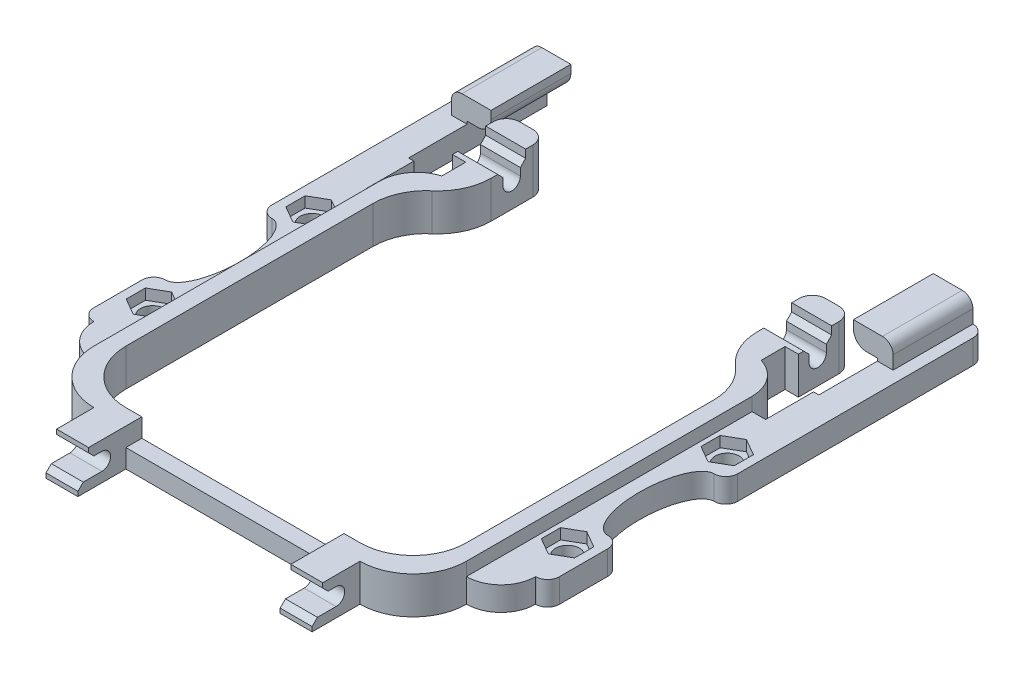
SolidWorks part; units mm, degrees
ref_plane "Front Plane" through (0, 0, 0) normal (0, 0, 1) x (1, 0, 0)
ref_plane "Top Plane" through (0, 0, 0) normal (0, 1, 0) x (1, 0, 0)
ref_plane "Right Plane" through (0, 0, 0) normal (1, 0, 0) x (0, 0, -1)
sketch "Sketch1" plane through (0, 0, 0) normal (0, 1, 0) x (1, 0, 0)
  line L0 (-19, -36) -> (-19, -19.5429) construction
  line L1 (-19, -36) -> (19, -36)
  line L3 (0, 36) -> (25, 36) construction
  line L4 (35, -36) -> (35, 36)
  line L5 (-35, -36) -> (35, 36) construction
  line L6 (-35, 36) -> (35, -36) construction
  line L7 (19, -36) -> (19, -19.5429) construction
  line L8 (0, 36) -> (0, -36) construction
  line L9 (19, -45) -> (25, -45)
  line L11 (-19, -36) -> (-19, -45)
  line L12 (-19, -45) -> (-25, -45)
  line L13 (-25, -36) -> (-25, -45)
  line L14 (25, -36) -> (25, -45)
  line L15 (19, -36) -> (19, -45)
  line L16 (-32.5, 40) -> (32.5, 40) construction
  line L17 (-41.1406, 49) -> (44.3921, 49) construction
  line L18 (-35, -36) -> (-25, -36)
  line L19 (-25, 36) -> (-25, 25.7143) construction
  line L20 (25, 36) -> (25, 25.7143) construction
  line L21 (25, -36) -> (35, -36) construction
  line L23 (-25, 36) -> (-25, 49)
  line L24 (-25, 49) -> (-32.5, 49)
  line L25 (-32.5, 36) -> (-32.5, 49)
  line L26 (-32, 33) -> (-32, -33)
  line L27 (25, 36) -> (25, 49)
  line L28 (25, 49) -> (32.5, 49)
  line L29 (32.5, 36) -> (32.5, 49)
  line L37 (-35, 36) -> (-32.5, 36)
  line L39 (35, 36) -> (32.5, 36)
  line L40 (-35, 36) -> (-35, -36)
  line L42 (25, -36) -> (35, -36)
  line L50 (32, -33) -> (32, 33)
  line L60 (-28, 33) -> (-28, 46) construction
  line L61 (-29.5, 33) -> (-29.5, 46) construction
  line L62 (-28, 46) -> (-29.5, 46) construction
  line L63 (29.5, 33) -> (29.5, 46) construction
  line L64 (28, 46) -> (29.5, 46) construction
  line L65 (28, 33) -> (28, 46) construction
  line L66 (22, -33) -> (22, -42) construction
  line L67 (22, -33) -> (22, -42) construction
  line L68 (22, -42) -> (22, -42) construction
  line L69 (-22, -33) -> (-22, -42) construction
  line L70 (-22, -33) -> (-22, -42) construction
  line L71 (-22, -42) -> (-22, -42) construction
  line L72 (-32, -33) -> (-22, -33) construction
  line L73 (22, -33) -> (32, -33) construction
  line L74 (-22, -33) -> (22, -33) construction
  line L75 (-32, 33) -> (-29.5, 33) construction
  line L76 (-28, 33) -> (28, 33) construction
  line L77 (32, 33) -> (29.5, 33) construction
  line L78 (-32, 33) -> (-25, 33)
  line L79 (-32, -33) -> (32, -33)
  line L80 (-25, 36) -> (-25, 33)
  line L81 (25, 36) -> (25, 33)
  line L82 (-25, 36) -> (0, 36) construction
  line L83 (-25, 36) -> (25, 36) construction
  line L85 (25, 33) -> (32, 33)
  dimension "D3" = 50
  dimension "D7" = 3
  dimension "D1" = 70
  dimension "D2" = 72
  dimension "D4" = 38
  dimension "D5" = 6
  dimension "D6" = 9
  dimension "D8" = 76
  dimension "D9" = 85
  dimension "D10" = 66
  dimension "D13" = 7.5
  dimension "D14" = 13
extrude "Boss-Extrude1" add sketch "Sketch1" along normal blind 7
sketch "Sketch2" plane through (25, 0, 0) normal (1, 0, 0) x (0, 0, -1)
  line L0 (-36, 0) -> (-45, 0) construction
  line L1 (-45, 7) -> (-36, 7)
  line L2 (-45, 7) -> (-45, 0)
  line L3 (-45, 0) -> (-36, 0)
  line L4 (-36, 7) -> (-36, 0)
  line L5 (-36, 7) -> (-36, 0) construction
  line L6 (-45, 7) -> (-36, 0) construction
  line L7 (-36, 7) -> (-45, 0) construction
  line L8 (-40.5, 5.125) -> (-45, 5.125)
  line L9 (-40.5, 1.875) -> (-45, 1.875)
  line L10 (-43, 5.125) -> (-43, 7)
  line L11 (-43, 7) -> (-45, 7)
  line L12 (-45, 5.125) -> (-45, 7)
  line L13 (-45, 5.125) -> (-43, 5.125)
  arc A0 (-40.5, 1.875) -> (-40.5, 5.125) centre (-40.5, 3.5) ccw
  line M7 (-45, 7) -> (-45, 0)
  dimension "D1" = 3.25
  dimension "D2" = 2
extrude "Cut-Extrude2" cut sketch "Sketch2" against normal up to surface (50 mm away) contours A0 | L8 L10 L1 M7 region at (25, 6.0625, 44) region at (25, 3.5, 42.1005) up to face at (-25, 3.5, 40.5)
sketch "Sketch3" plane through (32.5, 0, 0) normal (1, 0, 0) x (0, 0, -1)
  line L1 (49, 0) -> (36, 0)
  line L2 (49, 0) -> (49, 7)
  line L3 (49, 7) -> (36, 7)
  line L4 (36, 0) -> (36, 7)
  line L6 (44.125, 4.625) -> (44.125, 7)
  line L7 (40.875, 4.625) -> (40.875, 7)
  arc A0 (40.875, 4.625) -> (44.125, 4.625) centre (42.5, 4.625) ccw
  point P7 (42.5, 3)
  dimension "D1" = 3.25
  dimension "D2" = 3
sketch "Sketch4" plane through (0, 0, 0) normal (0, -1, 0) x (1, 0, 0)
  line L0 (0, -67.5) -> (0, 45) construction
  line L1 (41.5, 45) -> (-41.5, 45)
  line L3 (41.5, -67.5) -> (-41.5, -67.5)
  line L5 (19, 45) -> (25, 45) construction
  line L7 (-41.5, -5) -> (41.5, -5) construction
  line L13 (-41.5, 45) -> (-41.5, -67.5)
  line L15 (41.5, 45) -> (41.5, -67.5)
  point P0 (0, 0)
  dimension "D1" = 83
  dimension "D2" = 112.5
  dimension "D7" = 5
ref_plane "Plane1" through (0, 0, -33) normal (0, 0, 1) x (1, 0, 0)
extrude "Cut-Extrude5" cut sketch "Sketch3" against normal up to surface (65 mm away) from surface contours L7 A0 L6 L3 region at (32.5, 5.1564, -42.5) up to face at (-32.5, 3.5, -42.5) starting at face at (32.5, 3.5, -42.5)
sketch "Sketch9" plane through (0, 7, 0) normal (0, 1, 0) x (1, 0, 0)
  line L1 (35, 38.875) -> (30, 38.875)
  line L2 (35, 38.875) -> (35, 34.375)
  line L3 (35, 34.375) -> (30, 34.375)
  line L4 (30, 38.875) -> (30, 34.375)
  line L5 (25, 40.875) -> (32.5, 40.875) construction
  line L6 (35, -36) -> (35, 36) construction
  dimension "D1" = 2
  dimension "D2" = 4.5
  dimension "D3" = 5
ref_plane "Plane2" through (0, 0, 0) normal (-1, 0, 0) x (0, 0, 1)
extrude "Cut-Extrude8" cut sketch "Sketch9" against normal up to vertex (7 mm away) up to point (32.5, 0, -36)
mirror "Mirror1" about plane through (0, 0, 0) normal (-1, 0, 0) of "Cut-Extrude8"
fillet "Fillet1" radius 7 2 edges at (35, 3.5, -34.375) (-35, 3.5, -34.375)
fillet "Fillet3" radius 10 2 edges at (32, 3.5, -33) (-32, 3.5, -33)
fillet "Fillet5" radius 10 2 edges at (35, 3.5, 36) (-35, 3.5, 36)
fillet "Fillet6" radius 10 2 edges at (32, 3.5, 33) (-32, 3.5, 33)
fillet "Fillet7" radius 10 2 edges at (25, 3.5, -33) (-25, 3.5, -33)
fillet "Fillet8" radius 2.5 4 edges at (32.5, 3.5, -49) (25, 3.5, -49) (-25, 3.5, -49) (-32.5, 3.5, -49)
chamfer "Chamfer2" distance 1 angle 45 4 edges at (28.75, 7, -40.875) (28.75, 7, -44.125) (-28.75, 7, -40.875) (-28.75, 7, -44.125)
sketch "Sketch20" plane through (0, 0, 36) normal (0, 0, 1) x (1, 0, 0)
  line L0 (19, 7) -> (19, 0) construction
  line L1 (-19, 7) -> (19, 7)
  line L2 (-19, 7) -> (-19, 3.5)
  line L3 (-19, 3.5) -> (19, 3.5)
  line L4 (19, 7) -> (19, 3.5)
  dimension "D1" = 3.5
extrude "Cut-Extrude7" cut sketch "Sketch20" against normal up to next
sketch "Sketch22" plane through (-35, 0, 0) normal (-1, 0, 0) x (0, 0, 1)
  line L1 (-27.6668, 4.5) -> (26, 4.5)
  line L2 (-27.6668, 4.5) -> (-27.6668, 0)
  line L3 (-27.6668, 0) -> (26, 0)
  line L4 (26, 4.5) -> (26, 0)
  line L9 (-27.6668, 0) -> (26, 0) construction
  line L11 (-27.6668, 7) -> (-27.6668, 0) construction
  line L12 (26, 0) -> (26, 7) construction
  dimension "D1" = 4.5
extrude "Boss-Extrude9" add sketch "Sketch22" along normal up to vertex (6.5 mm away) up to point (-41.5, 0, 45)
sketch "Sketch24" plane through (0, 0, -27.6668) normal (0, 0, -1) x (-1, 0, 0)
  line L1 (41.5, 0) -> (37.55, 0)
  line L2 (41.5, 0) -> (41.5, 4.5)
  line L3 (41.5, 4.5) -> (37.55, 4.5)
  line L4 (37.55, 0) -> (37.55, 4.5)
  line L7 (41.5, 4.5) -> (35, 4.5) construction
  dimension "D1" = 3.95
extrude "Boss-Extrude11" add sketch "Sketch24" along normal blind 35
sketch "Sketch25" plane through (0, 4.5, 0) normal (0, 1, 0) x (1, 0, 0)
  line L0 (-41.5, -45) -> (-41.5, 67.5) construction
  line L1 (-37.55, 62.6668) -> (-41.5, 62.6668)
  line L2 (-37.55, 62.6668) -> (-37.55, 47.6668)
  line L3 (-37.55, 47.6668) -> (-41.5, 47.6668)
  line L4 (-41.5, 62.6668) -> (-41.5, 47.6668)
  dimension "D1" = 15
extrude "Boss-Extrude12" add sketch "Sketch25" along normal blind 4.5
sketch "Sketch28" plane through (-37.55, 0, 0) normal (1, 0, 0) x (0, 0, -1)
  line L1 (62.6668, 9) -> (47.6668, 9)
  line L2 (62.6668, 9) -> (62.6668, 5)
  line L3 (62.6668, 5) -> (47.6668, 5)
  line L4 (47.6668, 9) -> (47.6668, 5)
  dimension "D1" = 4
extrude "Boss-Extrude13" add sketch "Sketch28" along normal blind 3.5
fillet "Fillet16" radius 2 1 edges at (-41.5, 9, -55.1668)
fillet "Fillet17" radius 2.5 1 edges at (-34.05, 5, -55.1668)
hole_wizard "M4 Clearance Hole1" positions "Sketch31" profile "Sketch32" hole size "M4" standard "AS" end condition up to next
sketch "Sketch31" plane through (0, 4.5, 0) normal (0, 1, 0) x (1, 0, 0)
  line L2 (-39, -26) -> (-39, 47.6668) construction
  line L3 (-41.5, -26) -> (-35, -26) construction
  line L5 (-35, -26) -> (-35, 27.6668) construction
  line L6 (-41.5, 47.6668) -> (-37.55, 47.6668) construction
  point P2 (-39, -11)
  point P24 (-39, 19)
  dimension "D1" = 45
  dimension "D2" = 15
  dimension "D3" = 4
sketch "Sketch32" plane through (-39, 4.5, 11) normal (1, 0, 0) x (0, 0, 1)
  line L0 (0, 0) -> (0, 4.5)
  line L1 (0, 4.5) -> (2.25, 4.5)
  line L2 (2.25, 4.5) -> (2.25, 0.025)
  line L3 (2.25, 0.025) -> (2.275, 0)
  line L5 (2.275, 0) -> (0, 0)
  line L6 (-2.25, 0.025) -> (-2.275, 0) construction
  line L11 (0, -6.35) -> (0, 107.95) construction
  dimension "Thru Hole Dia." = 4.5
  dimension "Thru Hole Depth" = 4.5
  dimension "Near C'Sink Dia." = 4.55
  dimension "Near C'Sink Angle" = 90
sketch "Sketch33" plane through (0, 4.5, 0) normal (0, 1, 0) x (1, 0, 0)
  line L0 (-41.5, -26) -> (-41.5, 47.6668) construction
  circle A0 centre (-39, 19) radius 2.275 construction
  ellipse E0 centre (-41.5, 4) end of major axis (-41.5, 14) minor radius 4
  dimension "D1" = 15
  dimension "D2" = 10
  dimension "D3" = 4
extrude "Cut-Extrude9" cut sketch "Sketch33" against normal up to next contours E0
sketch "Sketch35" plane through (0, 0, -62.6668) normal (0, 0, -1) x (-1, 0, 0)
  line L0 (36.55, 5) -> (37.55, 5) construction
  line L1 (37.55, 0) -> (38.55, 0)
  line L2 (37.55, 0) -> (37.55, 5)
  line L3 (37.55, 5) -> (38.55, 5)
  line L4 (38.55, 0) -> (38.55, 5)
  dimension "D1" = 1
extrude "Cut-Extrude11" cut sketch "Sketch35" against normal blind 26
mirror "Mirror9" about plane through (0, 0, 0) normal (-1, 0, 0) of "Cut-Extrude11", "Cut-Extrude9", "Fillet17", "Boss-Extrude13", "Boss-Extrude9", "Boss-Extrude11", "Boss-Extrude12", "Fillet16", "M4 Clearance Hole1"
fillet "Fillet23" radius 6.5 2 edges at (-41.5, 2.25, 26) (41.5, 2.25, 26)
sketch "Sketch36" plane through (-41.5, 0, 0) normal (-1, 0, 0) x (0, 0, 1)
  line L0 (-62.6668, 0) -> (-62.6668, 7) construction
  line L1 (-14, 0) -> (-62.6668, 0)
  line L2 (-14, 0) -> (-14, 4.5)
  line L3 (-14, 4.5) -> (-62.6668, 4.5)
  line L4 (-62.6668, 0) -> (-62.6668, 4.5)
  line L5 (6, 0) -> (19.5, 0)
  line L6 (6, 0) -> (6, 4.5)
  line L7 (6, 4.5) -> (19.5, 4.5)
  line L8 (19.5, 0) -> (19.5, 4.5)
  dimension "D1" = 4.5
extrude "Boss-Extrude14" add sketch "Sketch36" along normal blind 2.25
fillet "Fillet24" radius 2.2 4 edges at (-43.75, 2.25, -62.6668) (-43.75, 2.25, -14) (-43.75, 2.25, 6) (-43.75, 2.25, 19.5)
sketch "Sketch37" plane through (0, 4.5, 0) normal (0, 1, 0) x (1, 0, 0)
  line L1 (-39, 22.6084) -> (-42.125, 20.8042)
  line L2 (-42.125, 20.8042) -> (-42.125, 17.1958)
  line L3 (-42.125, 17.1958) -> (-39, 15.3916)
  line L4 (-39, 15.3916) -> (-35.875, 17.1958)
  line L5 (-35.875, 17.1958) -> (-35.875, 20.8042)
  line L6 (-35.875, 20.8042) -> (-39, 22.6084)
  line L7 (-35, -26) -> (-35, 27.6668) construction
  line L8 (-35, 27.6668) -> (-35, -26) construction
  line L9 (-39, -7.3916) -> (-42.125, -9.1958)
  line L10 (-42.125, -9.1958) -> (-42.125, -12.8042)
  line L11 (-42.125, -12.8042) -> (-39, -14.6084)
  line L12 (-39, -14.6084) -> (-35.875, -12.8042)
  line L13 (-35.875, -12.8042) -> (-35.875, -9.1958)
  line L14 (-35.875, -9.1958) -> (-39, -7.3916)
  circle A0 centre (-39, 19) radius 3.125 construction
  circle A1 centre (-39, -11) radius 3.125 construction
  dimension "D1" = 6.25
  dimension "D2" = 6.25
extrude "Cut-Extrude12" cut sketch "Sketch37" against normal blind 2
mirror "Mirror10" about plane through (0, 0, 0) normal (-1, 0, 0) of "Cut-Extrude12", "Fillet24", "Boss-Extrude14"
sketch "Sketch38" plane through (0, 7, 0) normal (0, 1, 0) x (1, 0, 0)
  line L0 (-25, 45.125) -> (-25, 46.5) construction
  line L1 (-32.5, 45.125) -> (-25, 45.125)
  line L2 (-32.5, 45.125) -> (-32.5, 46.5)
  line L3 (-30, 49) -> (-27.5, 49)
  line L4 (-25, 45.125) -> (-25, 46.5)
  line L5 (-27.5, 49) -> (-30, 49) construction
  line L6 (25, 45.125) -> (32.5, 45.125)
  line L7 (25, 45.125) -> (25, 46.5)
  line L8 (27.5, 49) -> (30, 49)
  line L9 (32.5, 45.125) -> (32.5, 46.5)
  line L10 (32.5, 45.125) -> (32.5, 46.5) construction
  line L11 (25, 46.5) -> (25, 45.125) construction
  line L12 (30, 49) -> (27.5, 49) construction
  line L13 (25, 45.125) -> (32.5, 45.125) construction
  arc A0 (-27.5, 49) -> (-25, 46.5) centre (-27.5, 46.5) cw
  arc A1 (-32.5, 46.5) -> (-30, 49) centre (-30, 46.5) cw
  arc A2 (30, 49) -> (32.5, 46.5) centre (30, 46.5) cw
  arc A3 (25, 46.5) -> (27.5, 49) centre (27.5, 46.5) cw
  dimension "D1" = 2.5
  dimension "D2" = 2.5
extrude "Boss-Extrude15" add sketch "Sketch38" along normal blind 1.5
chamfer "Chamfer4" distance 1 angle 45 4 edges at (22, 5.125, 43) (22, 1.875, 45) (-22, 5.125, 43) (-22, 1.875, 45)
